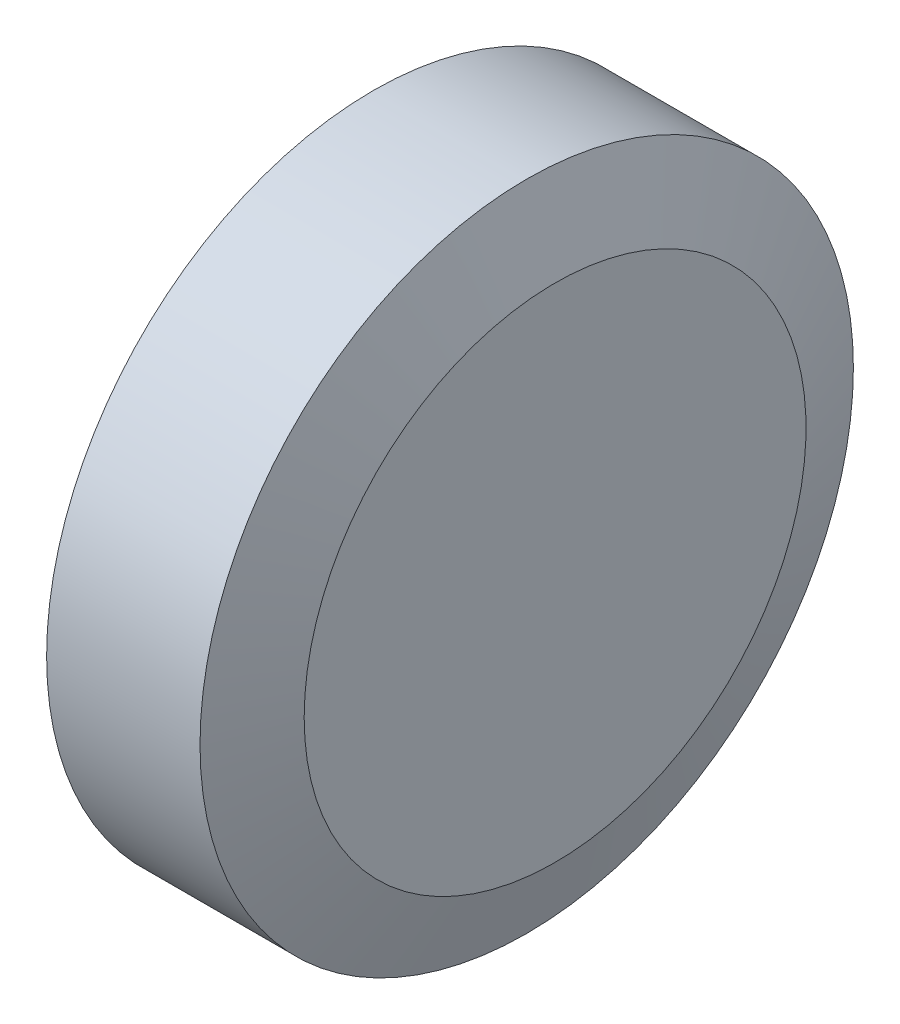
SolidWorks part; units mm, degrees
material "1060 Alloy"
ref_plane "Front Plane" through (0, 0, 0) normal (0, 0, 1) x (1, 0, 0)
ref_plane "Top Plane" through (0, 0, 0) normal (0, 1, 0) x (1, 0, 0)
ref_plane "Right Plane" through (0, 0, 0) normal (1, 0, 0) x (0, 0, -1)
sketch "Sketch1" plane through (0, 0, 0) normal (0, 0, 1) x (1, 0, 0)
  line L0 (-26.1347, 0) -> (27.2771, 0) construction
  line L1 (0, 0) -> (0, 26.5)
  line L6 (0, 26.5) -> (-3, 34.5)
  line L7 (-3, 34.5) -> (-19.2, 34.5)
  line L8 (-19.2, 34.5) -> (-19.2, 20.25)
  line L9 (-26.5, 0) -> (0, 0)
  line L10 (-19.2, 20.25) -> (-25.5, 20.25)
  line L11 (-25.5, 20.25) -> (-25.5, 16)
  line L12 (-25.5, 16) -> (-26.5, 16)
  line L13 (-26.5, 16) -> (-26.5, 0)
  dimension "D1" = 69
  dimension "D2" = 3
  dimension "D3" = 19.2
  dimension "D4" = 53
  dimension "D5" = 26.5
  dimension "D6" = 1
  dimension "D7" = 32
  dimension "D8" = 40.5
revolve "Revolve1" add sketch "Sketch1" angle 360 about L0
sketch "Sketch2" plane through (-25.5, 0, 0) normal (-1, 0, 0) x (0, 0, 1)
  line L0 (-13.1885, 18.8431) -> (-12.0917, 16.2435)
  line L1 (-11.5, 19.9186) -> (-10.125, 17.537) construction
  line L2 (-9.7244, 20.8431) -> (-8.0214, 18.5935)
  line L3 (13.1885, 18.8431) -> (12.0917, 16.2435)
  line L4 (9.7244, 20.8431) -> (8.0214, 18.5935)
  line L5 (22.9129, -2) -> (20.1132, -2.35)
  line L6 (22.9129, 2) -> (20.1132, 2.35)
  line L7 (9.7244, -20.8431) -> (8.0214, -18.5935)
  line L8 (13.1885, -18.8431) -> (12.0917, -16.2435)
  line L9 (-13.1885, -18.8431) -> (-12.0917, -16.2435)
  line L10 (-9.7244, -20.8431) -> (-8.0214, -18.5935)
  line L11 (-22.9129, 2) -> (-20.1132, 2.35)
  line L12 (-22.9129, -2) -> (-20.1132, -2.35)
  circle A0 centre (0, 0) radius 21 construction
  arc A1 (-9.7244, 20.8431) -> (-13.1885, 18.8431) centre (0, 0) ccw
  circle A2 centre (-10.5, 18.1865) radius 1.5
  arc A3 (-12.0917, 16.2435) -> (-20.1132, 2.35) centre (0, 0) ccw
  arc A4 (13.1885, 18.8431) -> (9.7244, 20.8431) centre (0, 0) ccw
  circle A5 centre (10.5, 18.1865) radius 1.5
  arc A6 (22.9129, -2) -> (22.9129, 2) centre (0, 0) ccw
  circle A7 centre (21, 0) radius 1.5
  arc A8 (9.7244, -20.8431) -> (13.1885, -18.8431) centre (0, 0) ccw
  circle A9 centre (10.5, -18.1865) radius 1.5
  arc A10 (-13.1885, -18.8431) -> (-9.7244, -20.8431) centre (0, 0) ccw
  circle A11 centre (-10.5, -18.1865) radius 1.5
  arc A12 (-22.9129, 2) -> (-22.9129, -2) centre (0, 0) ccw
  circle A13 centre (-21, 0) radius 1.5
  arc A14 (8.0214, 18.5935) -> (-8.0214, 18.5935) centre (0, 0) ccw
  arc A15 (20.1132, 2.35) -> (12.0917, 16.2435) centre (0, 0) ccw
  arc A16 (12.0917, -16.2435) -> (20.1132, -2.35) centre (0, 0) ccw
  arc A17 (-8.0214, -18.5935) -> (8.0214, -18.5935) centre (0, 0) ccw
  arc A18 (-20.1132, -2.35) -> (-12.0917, -16.2435) centre (0, 0) ccw
  point P45 (0, 0)
  circle M7 centre (0, 0) radius 16
  circle M8 centre (0, 0) radius 20.25
  dimension "D1" = 42
  dimension "D2" = 46
  dimension "D3" = 3
  dimension "D4" = 40.5
  dimension "D5" = 4
  dimension "D6" = 4.7
  dimension "D7" = 6
extrude "Boss-Extrude2" add sketch "Sketch2" against normal blind 3 separate body contours A9 M8 | A9 M8 | A11 M8 | A7 M8 | A7 M8 | A5 M8 | A5 M8 | A2 M8 | A2 M8 | A13 A11 A9 A7 A5 A2 M8 M7 | A12 L12 A18 L9 A10 L10 A17 L7 A8 L8 A16 L5 A6 L6 A15 L3 A4 L4 A14 L2 A1 L0 A3 L11 region at (-25.5, 16.0921, -11.3252) region at (-25.5, 17.264, -9.9674) region at (-25.5, 18.4037, -10.6254) region at (-25.5, 17.264, 9.9674) region at (-25.5, 18.4037, 10.6254) region at (-25.5, -17.264, -9.9674) region at (-25.5, 0, 19.9348) region at (-25.5, 0, 21.2507) region at (-25.5, -18.4037, 10.6254) region at (-25.5, -17.264, 9.9674)
extrude "Cut-Extrude1" cut sketch "Sketch2<3>" against normal up to surface (3 mm away) contours A13 M8 | A13 | A2 | A5 | A7 | A9 | A11 region at (-25.5, 0, -21.2507) up to face at (-22.5, 0, 0)
sketch "Sketch2<3>" plane through (-25.5, 0, 0) normal (-1, 0, 0) x (0, 0, 1) same geometry as "Sketch2"
fillet "Fillet1" radius 1 12 edges at (-24, 20.8431, 9.7244) (-24, 18.8431, 13.1885) (-24, 2, 22.9129) (-24, -2, 22.9129) (-24, -18.8431, 13.1885) (-24, -20.8431, 9.7244) (-24, -20.8431, -9.7244) (-24, -18.8431, -13.1885) (-24, -2, -22.9129) (-24, 2, -22.9129) (-24, 18.8431, -13.1885) (-24, 20.8431, -9.7244)
